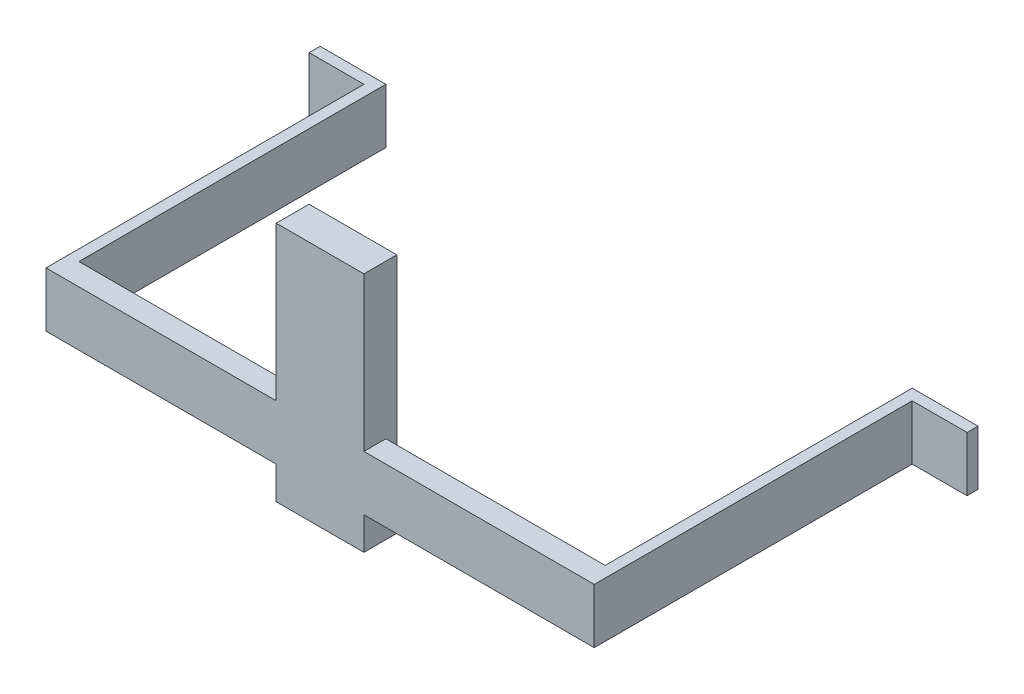
SolidWorks part; units mm, degrees
ref_plane "Front Plane" through (0, 0, 0) normal (0, 0, 1) x (1, 0, 0)
ref_plane "Top Plane" through (0, 0, 0) normal (0, 1, 0) x (1, 0, 0)
ref_plane "Right Plane" through (0, 0, 0) normal (1, 0, 0) x (0, 0, -1)
sketch "Sketch1" plane through (0, 0, 0) normal (0, 1, 0) x (1, 0, 0)
  line L0 (0, -55) -> (0, 55) construction
  line L1 (-25, -1) -> (25, -1)
  line L3 (-24, 1) -> (24, 1)
  line L8 (25, -1) -> (25, 28)
  line L11 (24, 29) -> (30, 29)
  line L13 (25, 28) -> (30, 28)
  line L14 (30, 29) -> (30, 28)
  line L15 (-25, -1) -> (-25, 28)
  line L16 (-30, 29) -> (-30, 28)
  line L17 (-25, 28) -> (-30, 28)
  line L19 (-24, 29) -> (-30, 29)
  line L20 (-24, 1) -> (-24, 29)
  line L22 (24, 1) -> (24, 29)
  point P0 (0, 0)
  dimension "D5" = 6
  dimension "D6" = 1
extrude "Boss-Extrude2" add sketch "Sketch1" along normal blind 5
sketch "Sketch3" plane through (0, 0, -1) normal (0, 0, -1) x (-1, 0, 0)
  line L0 (4.0055, 19.0254) -> (4.0055, -2.9746)
  line L5 (4.0055, -2.9746) -> (-3.9945, -2.9746)
  line L6 (3.0055, 18.0254) -> (-2.9945, 18.0254)
  line L7 (3.0055, 18.0254) -> (3.0055, -1.9746)
  line L8 (3.0055, -1.9746) -> (-2.9945, -1.9746)
  line L9 (-2.9945, 18.0254) -> (-2.9945, -1.9746)
  line L10 (-3.9945, 19.0254) -> (-3.9945, -2.9746)
  line L11 (4.0055, 19.0254) -> (-3.9945, 19.0254)
  point P4 (0, 0)
  point P5 (0, 0)
  point P9 (0, 1)
  dimension "D1" = 20
  dimension "D2" = 1
  dimension "D3" = 6
extrude "Boss-Extrude3" add sketch "Sketch3" along normal blind 1
sketch "Sketch5" plane through (0, 0, -1) normal (0, 0, 1) x (1, 0, 0)
  line L1 (-4.0055, 19.0254) -> (3.9945, 19.0254)
  line L2 (-4.0055, 19.0254) -> (-4.0055, -2.9746)
  line L3 (-4.0055, -2.9746) -> (3.9945, -2.9746)
  line L4 (3.9945, 19.0254) -> (3.9945, -2.9746)
extrude "Boss-Extrude5" add sketch "Sketch5" along normal up to surface (2 mm away) up to face at (0, 2.5, 1)
